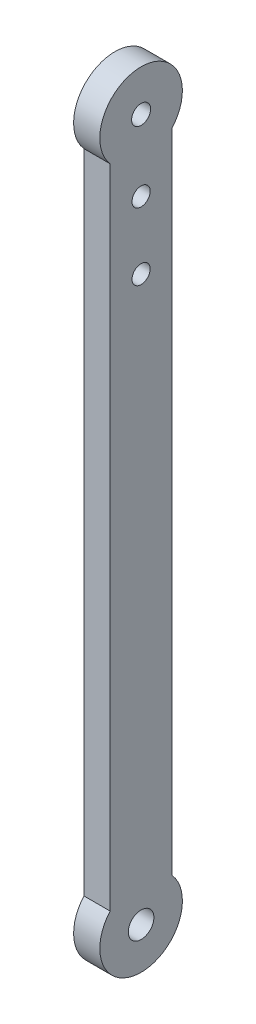
SolidWorks part; units mm, degrees
ref_plane "Front Plane" through (0, 0, 0) normal (0, 0, 1) x (1, 0, 0)
ref_plane "Top Plane" through (0, 0, 0) normal (0, 1, 0) x (1, 0, 0)
ref_plane "Right Plane" through (0, 0, 0) normal (1, 0, 0) x (0, 0, -1)
sketch "Sketch1" plane through (0, 0, 0) normal (1, 0, 0) x (0, 0, -1)
  line L0 (0, 0) -> (-3.75, -3.3072) construction
  line L2 (3.75, -3.3072) -> (3.75, -81.6928)
  line L3 (3.75, -81.6928) -> (-3.75, -81.6928) construction
  line L4 (-3.75, -3.3072) -> (-3.75, -81.6928)
  line L5 (3.75, -3.3072) -> (-3.75, -3.3072) construction
  line L6 (0, 0) -> (3.75, -3.3072) construction
  arc A1 (3.75, -3.3072) -> (-3.75, -3.3072) centre (0, 0) ccw
  arc A2 (-3.75, -81.6928) -> (3.75, -81.6928) centre (0, -85) ccw
  circle A3 centre (0, -85) radius 1.55
  circle A24 centre (0, -16.75) radius 1.1
  circle A264 centre (0, 0) radius 1.15
  circle A265 centre (0, -8.6) radius 1.1
  dimension "D1" = 2.3
  dimension "D2" = 10
  dimension "D4" = 10
  dimension "D6" = 3.1
  dimension "D7" = 2.2
  dimension "D3" = 7.5
  dimension "D5" = 85
  dimension "D8" = 8.15
  dimension "D9" = 8.6
extrude "Boss-Extrude3" add sketch "Sketch1" along normal blind 3.175
